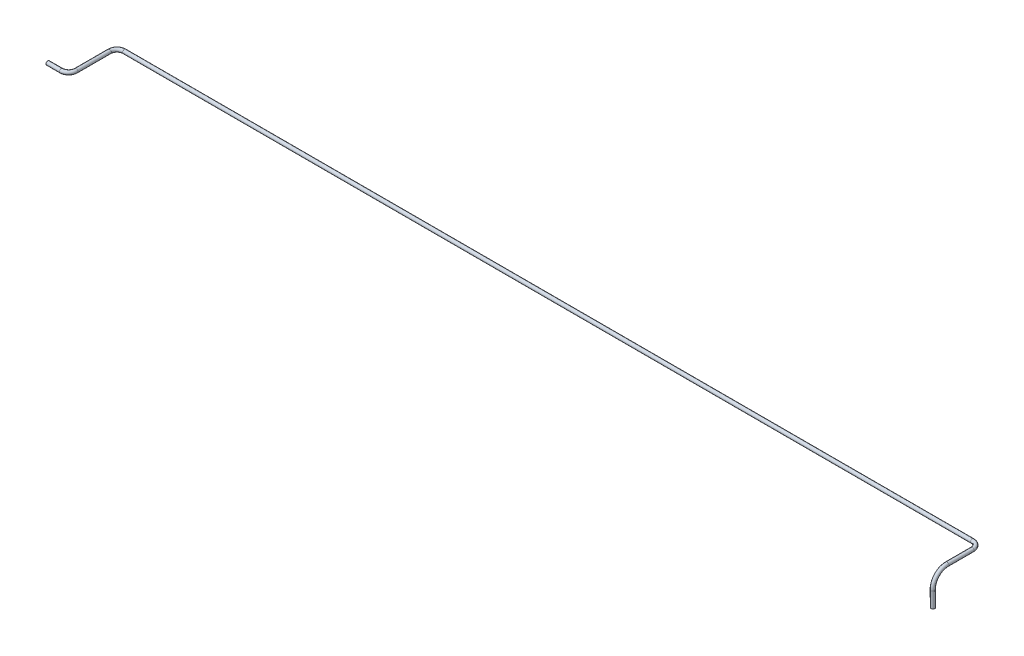
SolidWorks part; units mm, degrees
ref_plane "Front Plane" through (0, 0, 0) normal (0, 0, 1) x (1, 0, 0)
ref_plane "Top Plane" through (0, 0, 0) normal (0, 1, 0) x (1, 0, 0)
ref_plane "Right Plane" through (0, 0, 0) normal (1, 0, 0) x (0, 0, -1)
sketch3d "3DSketch1"
  line L1 (0, 0, 0) -> (22.86, 0, 0)
  line L2 (35.56, 0, -12.7) -> (35.56, 0, -69.85)
  line L3 (48.26, 0, -82.55) -> (1497.8807, 0, -82.55)
  line L4 (1510.5807, 0, -69.85) -> (1510.5807, 0, -26.7385)
  line L5 (1511.4548, -24.9414, -1.3424) -> (1512.3598, -50.7611, -0.8914)
  arc A0 (1510.5807, 0, -69.85) -> (1497.8807, 0, -82.55) centre (1497.8807, 0, -69.85) ccw
  arc A1 (35.56, 0, -69.85) -> (48.26, 0, -82.55) centre (48.26, 0, -69.85) ccw
  arc A2 (22.86, 0, 0) -> (35.56, 0, -12.7) centre (22.86, 0, -12.7) ccw
  arc A3 (1510.5807, 0, -26.7385) -> (1511.4548, -24.9414, -1.3424) centre (1511.4704, -25.3844, -26.7385) ccw
  point P9 (1510.5807, 0, -82.55)
  point P10 (1497.8807, 12.7, -69.85)
  point P12 (1510.5807, 0, -1.778)
  point P16 (35.56, 0, -82.55)
  point P17 (48.26, -12.7, -69.85)
  point P20 (35.56, 0, 0)
  point P22 (22.86, 12.7, -12.7)
  point P23 (1536.8548, -24.4948, -26.7385)
  dimension "D9" = 1513.2117
  dimension "D10" = 25.4
  dimension "D6" = 12.7
  dimension "D7" = 12.7
  dimension "D8" = 91
  dimension "D1" = 35.56
  dimension "D2" = 82.55
  dimension "D3" = 1475.0207
  dimension "D4" = 80.772
  dimension "D5" = 50.8
ref_plane "Plane4" through (0, 0, 0) normal (1, 0, 0) x (0, 0, -1)
sketch "Sketch5" plane through (0, 0, 0) normal (1, 0, 0) x (0, 0, -1)
  circle A0 centre (0, 0) radius 3.175
  circle A1 centre (0, 0) radius 2.667
  dimension "D1" = 6.35
  dimension "D2" = 0.508
sweep "Sweep3" add profiles "Sketch5" path "3DSketch1"
